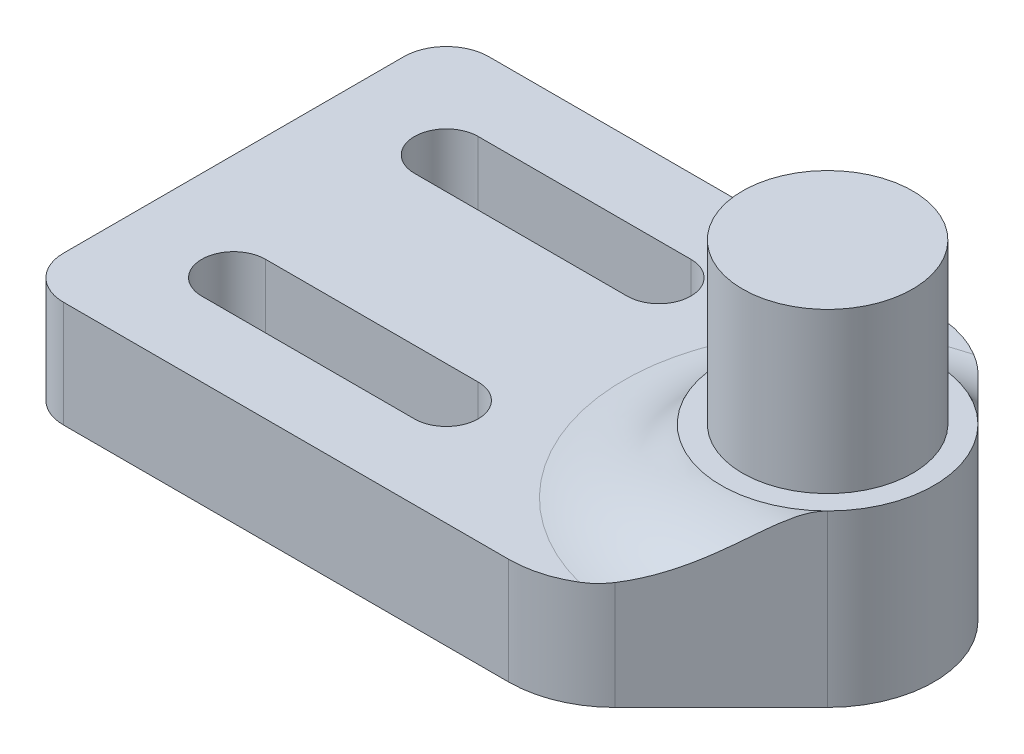
SolidWorks part; units mm, degrees
ref_plane "Front Plane" through (0, 0, 0) normal (0, 0, 1) x (1, 0, 0)
ref_plane "Top Plane" through (0, 0, 0) normal (0, 1, 0) x (1, 0, 0)
ref_plane "Right Plane" through (0, 0, 0) normal (1, 0, 0) x (0, 0, -1)
sketch "Sketch1" plane through (0, 0, 0) normal (0, 1, 0) x (1, 0, 0)
  line L0 (-12.5, 0) -> (12.5, 0) construction
  line L1 (-12.5, -10) -> (12.5, -10)
  line L2 (-12.5, -10) -> (-12.5, 10)
  line L3 (-12.5, 10) -> (12.5, 10)
  line L4 (12.5, -10) -> (12.5, 10)
  line L5 (-12.5, -10) -> (12.5, 10) construction
  line L6 (-12.5, 10) -> (12.5, -10) construction
  line L7 (-7.5, 5) -> (2.5, 5) construction
  line L8 (-7.5, 6.5) -> (2.5, 6.5)
  line L9 (-7.5, 3.5) -> (2.5, 3.5)
  line L10 (-2.5, 10) -> (-2.5, 0) construction
  line L11 (-7.5, -5) -> (2.5, -5) construction
  line L12 (-7.5, -6.5) -> (2.5, -6.5)
  line L13 (-7.5, -3.5) -> (2.5, -3.5)
  arc A0 (-7.5, 6.5) -> (-7.5, 3.5) centre (-7.5, 5) ccw
  arc A1 (2.5, 3.5) -> (2.5, 6.5) centre (2.5, 5) ccw
  arc A2 (-7.5, -6.5) -> (-7.5, -3.5) centre (-7.5, -5) cw
  arc A3 (2.5, -3.5) -> (2.5, -6.5) centre (2.5, -5) cw
  point P0 (0, 0)
  point P10 (-2.5, 5)
  point P19 (-2.5, -5)
  dimension "D1" = 3
  dimension "D2" = 10
  dimension "D3" = 25
  dimension "D4" = 20
  dimension "D5" = 10
extrude "Boss-Extrude1" add sketch "Sketch1" along normal blind 5
sketch "Sketch2" plane through (0, 5, 0) normal (0, 1, 0) x (1, 0, 0)
  line L0 (18.9645, -3.5355) -> (12.5, -10)
  line L1 (12.5, -10) -> (12.5, 10)
  line L2 (12.5, 10) -> (18.9645, 3.5355)
  arc A0 (18.9645, -3.5355) -> (18.9645, 3.5355) centre (15.4289, 0) ccw
  dimension "D1" = 10
  dimension "D2" = 45
extrude "Boss-Extrude2" add sketch "Sketch2" against normal up to surface (5 mm away) up to face at (0, 0, 0)
fillet "Fillet1" radius 5 2 edges at (12.5, 2.5, -10) (12.5, 2.5, 10)
sketch "Sketch3" plane through (0, 5, 0) normal (0, 1, 0) x (1, 0, 0)
  circle A0 centre (15.4289, 0) radius 5
extrude "Boss-Extrude3" add sketch "Sketch3" along normal blind 3
sketch "Sketch4" plane through (0, 8, 0) normal (0, 1, 0) x (1, 0, 0)
  circle A0 centre (15.4289, 0) radius 4
  dimension "D1" = 8
extrude "Boss-Extrude4" add sketch "Sketch4" along normal blind 7.5
fillet "Fillet2" radius 5 1 edges
fillet "Fillet3" radius 2 2 edges at (-12.5, 2.5, -10) (-12.5, 2.5, 10)
